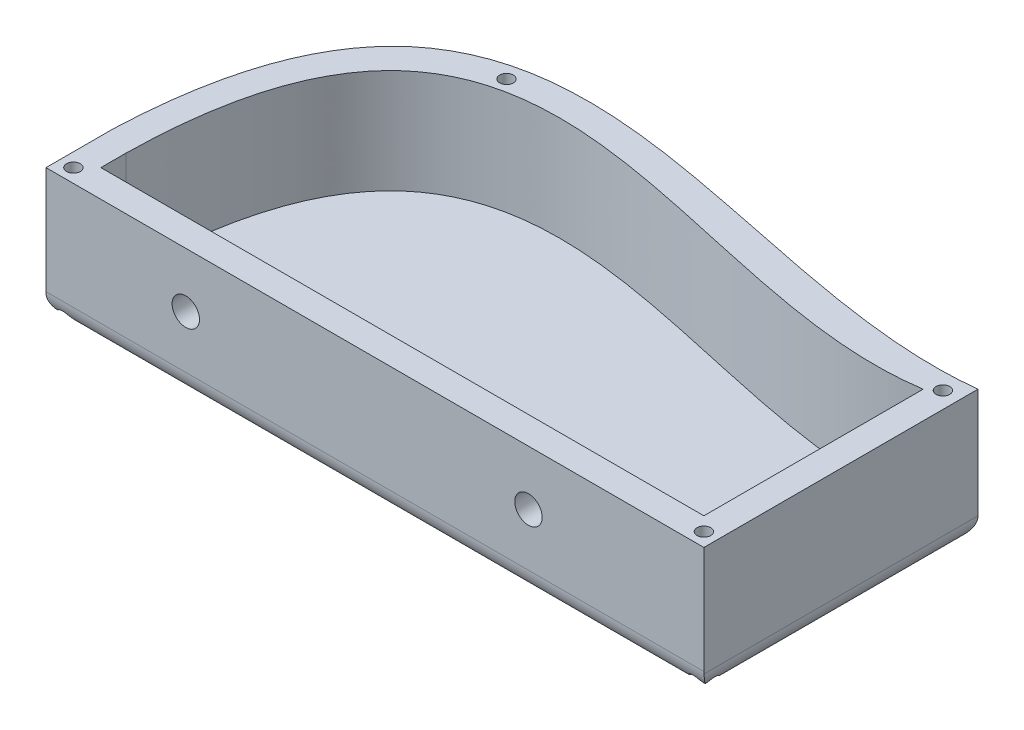
SolidWorks part; units mm, degrees
ref_plane "Front Plane" through (0, 0, 0) normal (0, 0, 1) x (1, 0, 0)
ref_plane "Top Plane" through (0, 0, 0) normal (0, 1, 0) x (1, 0, 0)
ref_plane "Right Plane" through (0, 0, 0) normal (1, 0, 0) x (0, 0, -1)
sketch "Sketch1" plane through (0, 0, 0) normal (0, 1, 0) x (1, 0, 0)
  line L1 (0, 0) -> (76.2, 0)
  line L2 (0, 0) -> (0, 38.1)
  line L3 (0, 38.1) -> (76.2, 38.1)
  line L4 (76.2, 0) -> (76.2, 38.1)
  spline S0 degree 3 poles (0, 0) (-2.1647, 62.6103) (45.4594, 28.2973) (76.2, 31.75) knots 0 0 0 0 1 1 1 1
  dimension "D3" = 18.796
  dimension "D5" = 104.394
  dimension "D1" = 76.2
  dimension "D2" = 38.1
  dimension "D4" = 31.75
  dimension "D6" = 19.304
  dimension "D7" = 33.02
extrude "Boss-Extrude1" add sketch "Sketch1" along normal blind 15.24 contours S0 L2 L1 L4
sketch "Sketch2" plane through (0, 0, 0) normal (0, -1, 0) x (1, 0, 0)
  line L1 (0, 0) -> (76.2, 0)
  line L2 (0, 0) -> (0, -38.1)
  line L3 (0, -38.1) -> (76.2, -38.1)
  line L4 (76.2, 0) -> (76.2, -38.1)
  line L9 (3.175, -3.175) -> (73.025, -3.175)
  line L10 (3.175, -3.175) -> (3.175, -29.8078)
  line L11 (3.175, -29.8078) -> (73.025, -29.8078)
  line L12 (73.025, -3.175) -> (73.025, -29.8078)
  spline S0 degree 3 poles (0, 0) (-2.1647, -62.6103) (45.4594, -28.2973) (76.2, -31.75) knots 0 0 0 0 1 1 1 1
  spline S2 degree 3 poles (3.175, -3.175) (2.3612, -57.3369) (45.979, -24.4463) (73.025, -28.575) knots 0 0 0 0 1 1 1 1
  dimension "D4" = 19.304
  dimension "D6" = 104.394
  dimension "D11" = 25.4
  dimension "D12" = 15.621
  dimension "D14" = 92.8132
  dimension "D1" = 76.2
  dimension "D2" = 38.1
  dimension "D3" = 18.796
  dimension "D5" = 33.02
  dimension "D7" = 31.75
  dimension "D8" = 3.175
  dimension "D9" = 3.175
  dimension "D10" = 3.175
  dimension "D13" = 19.304
  dimension "D15" = 26.67
sketch "Sketch3" plane through (0, 15.24, 0) normal (0, 1, 0) x (1, 0, 0)
  line L0 (0, 0) -> (76.2, 0) construction
  line L1 (73.025, 3.175) -> (3.175, 3.175)
  line L2 (73.025, 3.175) -> (73.025, 29.8078)
  line L3 (73.025, 29.8078) -> (3.175, 29.8078)
  line L4 (3.175, 3.175) -> (3.175, 29.8078)
  spline S0 degree 3 poles (73.025, 28.575) (45.979, 24.4463) (2.3612, 57.3369) (3.175, 3.175) knots 0 0 0 0 1 1 1 1
extrude "Cut-Extrude2" cut sketch "Sketch3" against normal blind 12.065 contours L2 S0 L3 L4 L1 | L3 S0
sketch "Sketch4" plane through (0, 0, 0) normal (0, 0, 1) x (1, 0, 0)
  line L2 (76.2, 15.24) -> (76.2, 0) construction
  line L7 (0, 15.24) -> (76.2, 15.24) construction
  circle A0 centre (16.1925, 8.89) radius 1.5875
  circle A1 centre (55.88, 8.89) radius 1.5875
  dimension "D1" = 3.175
  dimension "D2" = 39.6875
  dimension "D3" = 20.32
  dimension "D4" = 6.35
extrude "Cut-Extrude3" cut sketch "Sketch4" against normal blind 3.175
sketch "Sketch5" plane through (0, 15.24, 0) normal (0, 1, 0) x (1, 0, 0)
  line L0 (0, 0) -> (76.2, 0) construction
  line L1 (0, 0) -> (0, 7.7712) construction
  line L2 (76.2, 0) -> (76.2, 31.75) construction
  circle A0 centre (1.5875, 1.5875) radius 0.7937
  circle A1 centre (74.6125, 1.5875) radius 0.7937
  circle A2 centre (74.295, 29.591) radius 0.7937
  circle A3 centre (17.78, 35.56) radius 0.7937
  dimension "D5" = 1.5875
  dimension "D1" = 1.5875
  dimension "D2" = 1.5875
  dimension "D3" = 1.5875
  dimension "D4" = 1.5875
  dimension "D6" = 1.27
  dimension "D7" = 1.016
  dimension "D8" = 17.78
  dimension "D9" = 35.56
extrude "Cut-Extrude4" cut sketch "Sketch5" against normal through all
sketch "Sketch6" plane through (0, 0, 0) normal (0, -1, 0) x (1, 0, 0)
  circle A1 centre (74.6125, -1.5875) radius 1.27
  circle A2 centre (1.5875, -1.5875) radius 1.27
  circle A3 centre (17.78, -35.56) radius 1.27
  circle A4 centre (74.295, -29.591) radius 1.27
  dimension "D5" = 2.54
extrude "Cut-Extrude5" cut sketch "Sketch6" against normal blind 2.54
fillet "Fillet3" radius 2.54 2 edges at (0, 0, -3.8856)
fillet "Fillet4" radius 2.54 3 edges at (76.2, 0, -14.5975) (76.2, 0.5622, -30.7979)
fillet "Fillet5" radius 2.794 7 edges at (75.8805, 1.3068, -1.658) (75.4561, 0.7439, 0) (2.8575, 0, -1.5875) (73.3425, 0, -1.5875) (38.1, 0, 0) (0.3195, 1.3068, -1.517) (0.7439, 0.7439, 0)
